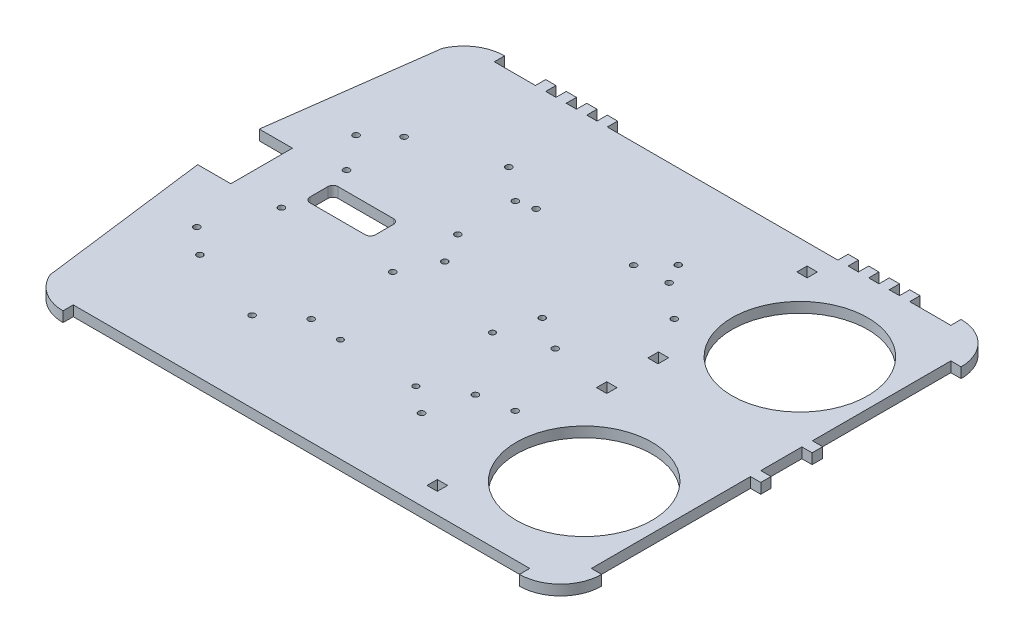
SolidWorks part; units mm, degrees
ref_plane "Front Plane" through (0, 0, 0) normal (0, 0, 1) x (1, 0, 0)
ref_plane "Top Plane" through (0, 0, 0) normal (0, 1, 0) x (1, 0, 0)
ref_plane "Right Plane" through (0, 0, 0) normal (1, 0, 0) x (0, 0, -1)
sketch "main_base_sketch" plane through (0, 0, 0) normal (0, 1, 0) x (1, 0, 0)
  line L0 (-111.125, -93.1364) -> (-111.125, 0) construction
  line L1 (111.125, 92.1224) -> (111.125, 23.3533) construction
  line L2 (111.125, -38.1761) -> (111.125, 0) construction
  line L3 (111.125, -99.4864) -> (111.125, -136.525) construction
  line L4 (111.125, -38.1761) -> (111.125, -99.4864) construction
  line L5 (111.125, 23.3533) -> (111.125, 0) construction
  line L7 (111.125, 92.1224) -> (111.125, 23.3533) construction
  line L8 (-111.125, -93.1364) -> (-111.125, -112.1864) construction
  line L9 (111.125, 0) -> (111.125, 23.3533) construction
  line L10 (111.125, 0) -> (111.125, -38.1761) construction
  line L11 (111.125, 0) -> (111.125, -38.1761) construction
  line L12 (-111.125, 0) -> (-111.125, 78.3136) construction
  line L13 (-131.6122, 15.1604) -> (-150.0052, 15.1604) construction
  line L14 (-111.125, 15.1604) -> (-131.6122, 15.1604)
  line L15 (-111.125, 15.1604) -> (-111.125, -22.9396)
  line L16 (-111.125, -22.9396) -> (-131.6122, -22.9396)
  line L17 (-150.0052, 15.1604) -> (-150.0052, -22.9396) construction
  line L19 (-131.6122, -22.9396) -> (-150.0052, -22.9396) construction
  line L20 (-111.125, 0) -> (111.125, 0) construction
  line L21 (-118.24, 114.9844) -> (-131.6122, 15.1604)
  line L22 (111.125, 130.2224) -> (117.475, 130.2224) construction
  line L24 (-94.9614, 130.2224) -> (-94.9614, 123.8724)
  line L25 (-94.9614, 123.8724) -> (-69.5614, 123.8724)
  line L26 (187.325, 130.2224) -> (187.325, 123.8724)
  line L27 (-94.9614, -142.875) -> (111.125, -142.875) construction
  line L28 (-94.9614, -142.875) -> (-94.9614, -136.525)
  line L29 (-94.9614, -136.525) -> (187.325, -136.525)
  line L30 (187.325, -142.875) -> (187.325, -136.525)
  line L31 (-131.6122, -22.9396) -> (-118.266, -127.5773)
  line L32 (-94.9614, 130.2224) -> (-25.1114, 130.2224) construction
  line L33 (111.125, -142.875) -> (187.325, -142.875) construction
  line L34 (111.125, -136.525) -> (111.125, -142.875) construction
  line L36 (111.125, -136.525) -> (111.125, -142.875) construction
  line L37 (-56.8614, 130.2224) -> (-50.5114, 130.2224)
  line L38 (111.125, 12.7) -> (117.4276, 12.7)
  line L39 (-42.259, -8.6817) -> (-76.4089, -8.6817)
  line L40 (-39.084, -5.5067) -> (-39.084, 5.5067)
  line L41 (-42.259, 8.6817) -> (-76.4089, 8.6817)
  line L42 (-79.5839, -5.5067) -> (-79.5839, 5.5067)
  line L43 (-39.084, -8.6817) -> (-79.5839, 8.6817) construction
  line L44 (-39.084, 8.6817) -> (-79.5839, -8.6817) construction
  line L45 (-111.125, 78.3136) -> (-111.125, 84.6636) construction
  line L46 (61.595, 63.5) -> (93.345, 63.5) construction
  line L47 (61.595, 63.5) -> (61.595, -63.5) construction
  line L48 (61.595, -63.5) -> (93.345, -63.5) construction
  line L49 (93.345, 63.5) -> (93.345, -63.5) construction
  line L50 (61.595, 63.5) -> (93.345, -63.5) construction
  line L51 (61.595, -63.5) -> (93.345, 63.5) construction
  line L52 (111.125, 12.7) -> (111.125, 19.2555)
  line L53 (111.125, 23.3533) -> (111.125, 0) construction
  line L54 (111.125, 19.2555) -> (117.4276, 19.2555)
  line L55 (-94.9614, 130.2224) -> (-25.1114, 130.2224) construction
  line L56 (-111.125, 122.7636) -> (-111.125, 84.6636) construction
  line L58 (111.125, 123.8724) -> (111.125, 92.1224) construction
  line L60 (-111.125, -112.1864) -> (-111.125, -150.2864) construction
  line L61 (-94.9614, -142.875) -> (111.125, -142.875) construction
  line L62 (111.125, -99.4864) -> (111.125, -136.525) construction
  line L63 (111.125, 130.2224) -> (117.475, 130.2224) construction
  line L64 (111.125, 123.8724) -> (111.125, 92.1224) construction
  line L65 (111.125, -142.875) -> (187.325, -142.875) construction
  line L66 (212.725, 104.8224) -> (212.725, -117.475) construction
  line L67 (117.4276, 12.7) -> (117.4276, 19.2555)
  line L68 (111.125, -12.7) -> (117.475, -12.7)
  line L69 (111.125, -12.7) -> (111.125, -19.05)
  line L70 (111.125, -19.05) -> (117.475, -19.05)
  line L71 (117.475, -12.7) -> (117.475, -19.05)
  line L72 (111.125, 104.8224) -> (117.475, 104.8224)
  line L73 (111.125, 104.8224) -> (111.125, 111.1724)
  line L74 (111.125, 111.1724) -> (117.475, 111.1724)
  line L75 (117.475, 104.8224) -> (117.475, 111.1724)
  line L76 (111.125, -117.475) -> (117.475, -117.475)
  line L77 (111.125, -117.475) -> (111.125, -123.825)
  line L78 (111.125, -123.825) -> (117.475, -123.825)
  line L79 (117.475, -117.475) -> (117.475, -123.825)
  line L80 (212.725, 104.8224) -> (206.375, 104.8224)
  line L81 (212.725, 104.8224) -> (212.725, -117.475) construction
  line L82 (212.725, -117.475) -> (206.375, -117.475)
  line L84 (-69.5614, 130.2224) -> (-63.2114, 130.2224)
  line L85 (-69.5614, 130.2224) -> (-69.5614, 123.8724)
  line L86 (-69.5614, 123.8724) -> (-63.2114, 123.8724) construction
  line L87 (-63.2114, 130.2224) -> (-63.2114, 123.8724)
  line L88 (-56.8614, 130.2224) -> (-56.8614, 123.8724)
  line L89 (-56.8614, 123.8724) -> (-50.5114, 123.8724) construction
  line L90 (-50.5114, 130.2224) -> (-50.5114, 123.8724)
  line L91 (-44.1614, 130.2224) -> (-37.8114, 130.2224)
  line L92 (-44.1614, 130.2224) -> (-44.1614, 123.8724)
  line L93 (-44.1614, 123.8724) -> (-37.8114, 123.8724) construction
  line L94 (-37.8114, 130.2224) -> (-37.8114, 123.8724)
  line L95 (-31.4614, 130.2224) -> (-25.1114, 130.2224)
  line L96 (-31.4614, 130.2224) -> (-31.4614, 123.8724)
  line L97 (-31.4614, 123.8724) -> (-25.1114, 123.8724) construction
  line L98 (-25.1114, 130.2224) -> (-25.1114, 123.8724)
  line L99 (-69.5614, 123.8724) -> (-63.2114, 123.8724) construction
  line L100 (-63.2114, 123.8724) -> (-56.8614, 123.8724)
  line L101 (-56.8614, 123.8724) -> (-50.5114, 123.8724) construction
  line L102 (-50.5114, 123.8724) -> (-44.1614, 123.8724)
  line L103 (-44.1614, 123.8724) -> (-37.8114, 123.8724) construction
  line L104 (-37.8114, 123.8724) -> (-31.4614, 123.8724)
  line L105 (-31.4614, 123.8724) -> (-25.1114, 123.8724) construction
  line L106 (-25.1114, 123.8724) -> (117.475, 123.8724)
  line L107 (149.225, 130.2224) -> (142.875, 130.2224)
  line L108 (161.925, 130.2224) -> (155.575, 130.2224)
  line L109 (161.925, 130.2224) -> (161.925, 123.8724)
  line L110 (161.925, 123.8724) -> (155.575, 123.8724) construction
  line L111 (155.575, 130.2224) -> (155.575, 123.8724)
  line L112 (149.225, 130.2224) -> (149.225, 123.8724)
  line L114 (142.875, 130.2224) -> (142.875, 123.8724)
  line L115 (136.525, 130.2224) -> (130.175, 130.2224)
  line L116 (136.525, 130.2224) -> (136.525, 123.8724)
  line L118 (130.175, 130.2224) -> (130.175, 123.8724)
  line L119 (123.825, 130.2224) -> (117.475, 130.2224) construction
  line L120 (123.825, 130.2224) -> (123.825, 123.8724)
  line L122 (117.475, 130.2224) -> (117.475, 123.8724) construction
  line L123 (117.475, 130.2224) -> (123.825, 130.2224) construction
  line L124 (206.375, 104.8224) -> (206.375, 24.1792)
  line L127 (117.475, 130.2224) -> (117.475, 123.8724) construction
  line L128 (117.475, 130.2224) -> (117.475, 123.8724) construction
  line L129 (145.8534, 123.8724) -> (130.175, 123.8724) [skipped]
  line L130 (149.225, 123.8724) -> (146.7264, 123.8724) [skipped]
  line L131 (123.825, 123.8724) -> (130.175, 123.8724)
  line L132 (136.525, 123.8724) -> (142.875, 123.8724)
  line L133 (149.225, 123.8724) -> (155.575, 123.8724)
  line L134 (161.925, 123.8724) -> (187.325, 123.8724)
  line L135 (133.0367, 123.8724) -> (117.475, 123.8724) [skipped]
  line L136 (123.825, 130.2224) -> (187.325, 130.2224) construction
  line L137 (117.475, 130.2224) -> (123.825, 130.2224) construction
  line L138 (123.825, 130.2224) -> (187.325, 130.2224) construction
  line L139 (-25.1114, 130.2224) -> (111.125, 130.2224) construction
  line L140 (-25.1114, 130.2224) -> (111.125, 130.2224) construction
  line L141 (111.125, 130.2224) -> (111.125, 123.8724) construction
  line L142 (111.125, 130.2224) -> (111.125, 123.8724) construction
  line L143 (123.825, 130.2224) -> (117.475, 130.2224)
  line L144 (117.475, 130.2224) -> (117.475, 123.8724)
  line L151 (206.375, -12.7) -> (212.725, -12.7)
  line L152 (206.375, -12.7) -> (206.375, -19.05) construction
  line L153 (206.375, -19.05) -> (212.725, -19.05)
  line L154 (212.725, -12.7) -> (212.725, -19.05)
  line L155 (206.375, -12.7) -> (206.375, -19.05) construction
  line L156 (206.375, -19.05) -> (206.375, -117.475)
  line L157 (206.375, 19.2555) -> (212.725, 19.2555)
  line L158 (212.725, 19.2555) -> (212.725, 12.7)
  line L159 (212.725, 12.7) -> (206.375, 12.7)
  line L160 (206.375, 24.1792) -> (206.375, 19.2555)
  line L161 (206.375, 12.7) -> (206.375, -12.7)
  circle A0 centre (-82.6643, 55.7457) radius 1.905
  circle A1 centre (-13.8303, 55.7457) radius 1.905
  arc A2 (-76.4089, -8.6817) -> (-79.5839, -5.5067) centre (-76.4089, -5.5067) cw
  arc A3 (-42.259, -8.6817) -> (-39.084, -5.5067) centre (-42.259, -5.5067) ccw
  arc A4 (-39.084, 5.5067) -> (-42.259, 8.6817) centre (-42.259, 5.5067) ccw
  arc A5 (-76.4089, 8.6817) -> (-79.5839, 5.5067) centre (-76.4089, 5.5067) ccw
  arc A8 (-131.6122, 15.1604) -> (-131.6122, -22.9396) centre (172.5919, -3.8896) ccw construction
  arc A9 (-118.24, 114.9844) -> (-94.9614, 130.2224) centre (-94.9614, 104.8224) cw
  circle A10 centre (-3.2843, 57.9936) radius 1.905
  circle A11 centre (-13.8303, 20.1549) radius 1.905
  circle A12 centre (-3.2843, 1.5294) radius 1.905
  circle A13 centre (-82.6643, 20.1549) radius 1.905
  circle A14 centre (-82.6643, -20.1549) radius 1.905
  circle A15 centre (-13.8303, -20.1549) radius 1.905
  circle A16 centre (-82.6643, -70.5685) radius 1.905
  circle A17 centre (-13.8303, -70.5685) radius 1.905
  circle A18 centre (6.29, -72.5476) radius 1.796
  circle A19 centre (54.55, -74.1351) radius 1.796
  circle A20 centre (49.47, -21.7476) radius 1.796
  circle A21 centre (57.0407, 1.5294) radius 1.905
  circle A22 centre (57.0407, 57.9936) radius 1.905
  circle A23 centre (-98.425, 41.8224) radius 1.905
  circle A24 centre (-34.0871, 71.9636) radius 1.905
  circle A25 centre (70.6863, 71.9636) radius 1.905
  circle A26 centre (98.425, 41.8224) radius 1.905
  circle A27 centre (98.425, -56.6452) radius 1.905
  circle A28 centre (70.6863, -86.7864) radius 1.905
  circle A29 centre (-34.0871, -86.7864) radius 1.905
  circle A30 centre (-98.425, -56.6452) radius 1.905
  circle A31 centre (77.47, -60.325) radius 1.905
  circle A32 centre (77.47, 59.5313) radius 1.905
  circle A33 centre (77.47, -10.9537) radius 1.905
  arc A34 (212.725, -117.475) -> (187.325, -142.875) centre (187.325, -117.475) cw
  arc A35 (212.725, 104.8224) -> (187.325, 130.2224) centre (187.325, 104.8224) ccw
  arc A36 (-118.266, -127.5773) -> (-94.9614, -142.875) centre (-94.9614, -117.475) ccw
  circle A37 centre (157.48, 60.3724) radius 41.91
  circle A38 centre (157.48, -73.025) radius 41.91
  point P19 (212.725, -142.875)
  point P40 (-59.334, 0)
  point P111 (77.47, -63.5)
  point P113 (77.47, 0)
  point P123 (0, 0)
  point P142 (-69.5614, 127.0474)
  point P159 (187.325, 127.0474)
  point P182 (-131.6694, 14.7335)
  point P189 (-131.6122, -22.9396)
  dimension "D1" = 3.175
  dimension "D44" = 3.81
  dimension "D45" = 3.81
  dimension "D46" = 3.81
  dimension "D47" = 3.592
  dimension "D48" = 3.592
  dimension "D49" = 3.592
  dimension "D7" = 63.5
  dimension "D12" = 25.4
  dimension "D13" = 25.4
  dimension "D21" = 63.5
  dimension "D24" = 83.82
  dimension "D26" = 83.82
  dimension "D4" = 222.25
  dimension "D6" = 38.1
  dimension "D8" = 31.5411
  dimension "D9" = 40.4999
  dimension "D10" = 17.3633
  dimension "D11" = 28.4607
  dimension "D14" = 77.0379
  dimension "D15" = 104.7734
  dimension "D16" = 74.077
  dimension "D17" = 104.835
  dimension "D18" = 12.7
  dimension "D19" = 6.35
  dimension "D20" = 6.35
  dimension "D22" = 40.4387
  dimension "D23" = 54.0843
  dimension "D25" = 60.325
  dimension "D27" = 97.2947
  dimension "D28" = 77.0379
  dimension "D29" = 6.5555
  dimension "D30" = 28.4607
  dimension "D31" = 12.7
  dimension "D32" = 6.35
  dimension "D33" = 6.35
  dimension "D34" = 68.834
  dimension "D35" = 48.26
  dimension "D36" = 28.4607
  dimension "D37" = 20.1549
  dimension "D38" = 20.1549
  dimension "D39" = 56.4642
  dimension "D40" = 35.7997
  dimension "D41" = 54.0843
  dimension "D42" = 61.655
  dimension "D43" = 23.277
  dimension "D50" = 1.5875
  dimension "D51" = 127
  dimension "D52" = 31.75
  dimension "D53" = 17.78
  dimension "D54" = 3.175
  dimension "D55" = 3.9688
  dimension "D56" = 70.485
  dimension "D57" = 38.1
  dimension "D58" = 38.1
  dimension "D59" = 101.6
  dimension "D60" = 6.3026
  dimension "D61" = 12.7
  dimension "D62" = 12.7
  dimension "D63" = 6.35
  dimension "D64" = 6.35
  dimension "D65" = 6.35
  dimension "D66" = 6.35
  dimension "D67" = 12.7
  dimension "D68" = 12.7
  dimension "D69" = 6.35
  dimension "D70" = 6.35
  dimension "D71" = 4
  dimension "D72" = 25.4
  dimension "D73" = 6.35
  dimension "D74" = 25.4
  dimension "D75" = 4
extrude "main_base" add sketch "main_base_sketch" along normal blind 6.35
